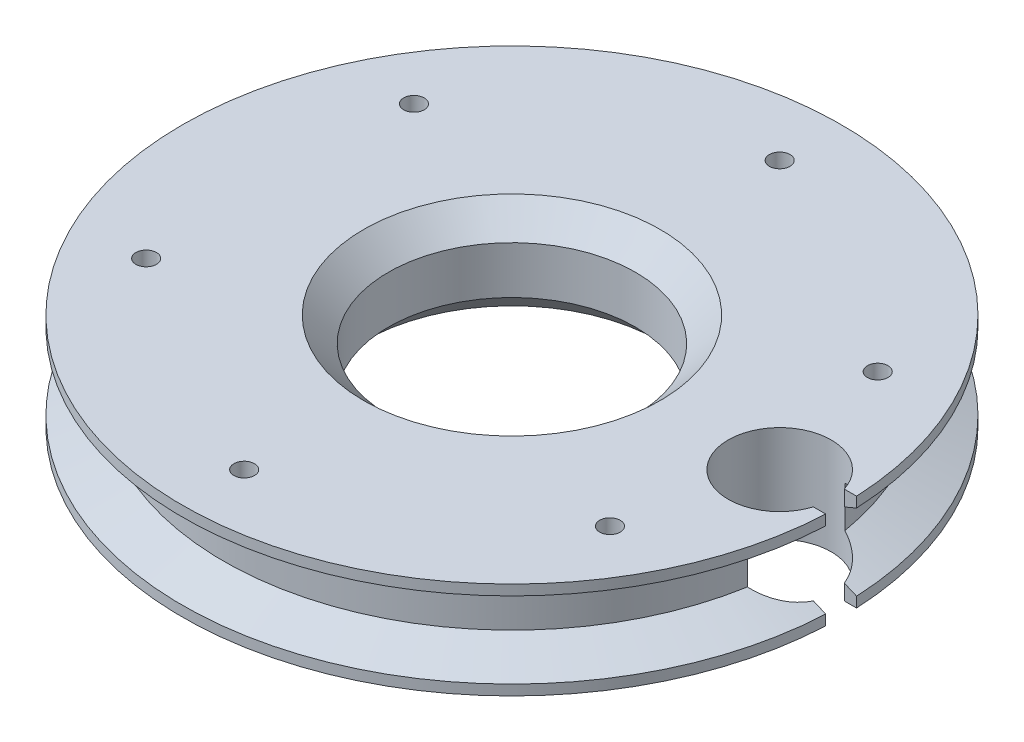
SolidWorks part; units mm, degrees
ref_plane "Plano frontal" through (0, 0, 0) normal (0, 0, 1) x (1, 0, 0)
ref_plane "Plano superior" through (0, 0, 0) normal (0, 1, 0) x (1, 0, 0)
ref_plane "Plano direito" through (0, 0, 0) normal (1, 0, 0) x (0, 0, -1)
sketch "Esboço2" plane through (0, 0, 0) normal (0, 0, 1) x (1, 0, 0)
  line L0 (6, 0) -> (16, 0)
  line L1 (16, 0) -> (16, 0.5)
  line L2 (16, 0.5) -> (14, 1.3527)
  line L3 (14, 1.3527) -> (14, 3.3527)
  line L4 (14, 3.3527) -> (16, 4.2053)
  line L5 (16, 4.2053) -> (16, 4.7053)
  line L8 (16, 4.7053) -> (6, 4.7053)
  line L11 (6, 4.7053) -> (6, 0)
  line L12 (0, 0) -> (0, 4.7053) construction
  dimension "D2" = 2
  dimension "D3" = 0.5
  dimension "D4" = 0.5
  dimension "D5" = 2
  dimension "D6" = 2
  dimension "D7" = 6
  dimension "D8" = 10
  dimension "D9" = 4.7053
  dimension "D10" = 113.09
  dimension "D11" = 113.09
revolve "Revolução1" add sketch "Esboço2" angle 360 about L12
sketch "Esboço3" plane through (0, 0, 0) normal (0, -1, 0) x (1, 0, 0)
  line L0 (13, 0) -> (25.9427, 0) construction
  line L1 (16.115, 0.75) -> (16.115, -0.75)
  line L2 (16.115, 0.75) -> (15.3848, 0.75)
  line L3 (16.115, -0.75) -> (15.3848, -0.75)
  arc A1 (15.3848, 0.75) -> (15.3848, -0.75) centre (13, 0) ccw
  point P8 (16.115, 0)
  dimension "D1" = 5
  dimension "D2" = 13
  dimension "D3" = 1.5
  dimension "D4" = 3.115
extrude "Corte-extrusão1" cut sketch "Esboço3" against normal blind 10
chamfer "Chanfro3" distance 1.2 angle 45 2 edges at (0, 0, -6) (0, 4.7053, -6)
sketch "Esboço5" plane through (0, 4.7053, 0) normal (0, 1, 0) x (1, 0, 0)
  circle A0 centre (0, 13) radius 0.5
  circle A1 centre (0, -13) radius 0.5
  circle A2 centre (0, 0) radius 13
  circle A4 centre (11.2583, 6.5) radius 0.5
  circle A5 centre (-11.2583, -6.5) radius 0.5
  circle A6 centre (11.2583, -6.5) radius 0.5
  circle A7 centre (-11.2583, 6.5) radius 0.5
  circle A8 centre (0, -13) radius 0.5
  circle A9 centre (0, 13) radius 0.5
  circle A10 centre (-11.2583, -6.5) radius 0.5
  circle A11 centre (11.2583, 6.5) radius 0.5
  circle A12 centre (-11.2583, 6.5) radius 0.5
  circle A13 centre (11.2583, -6.5) radius 0.5
  point P29 (0, 0)
  dimension "D1" = 1
  dimension "D3" = 1
  dimension "D5" = 26
  dimension "D2" = 6
extrude "Corte-extrusão2" cut sketch "Esboço5" against normal through all both and the other way through all contours A0 | A7 | A5 | A4 | A6 | A1
